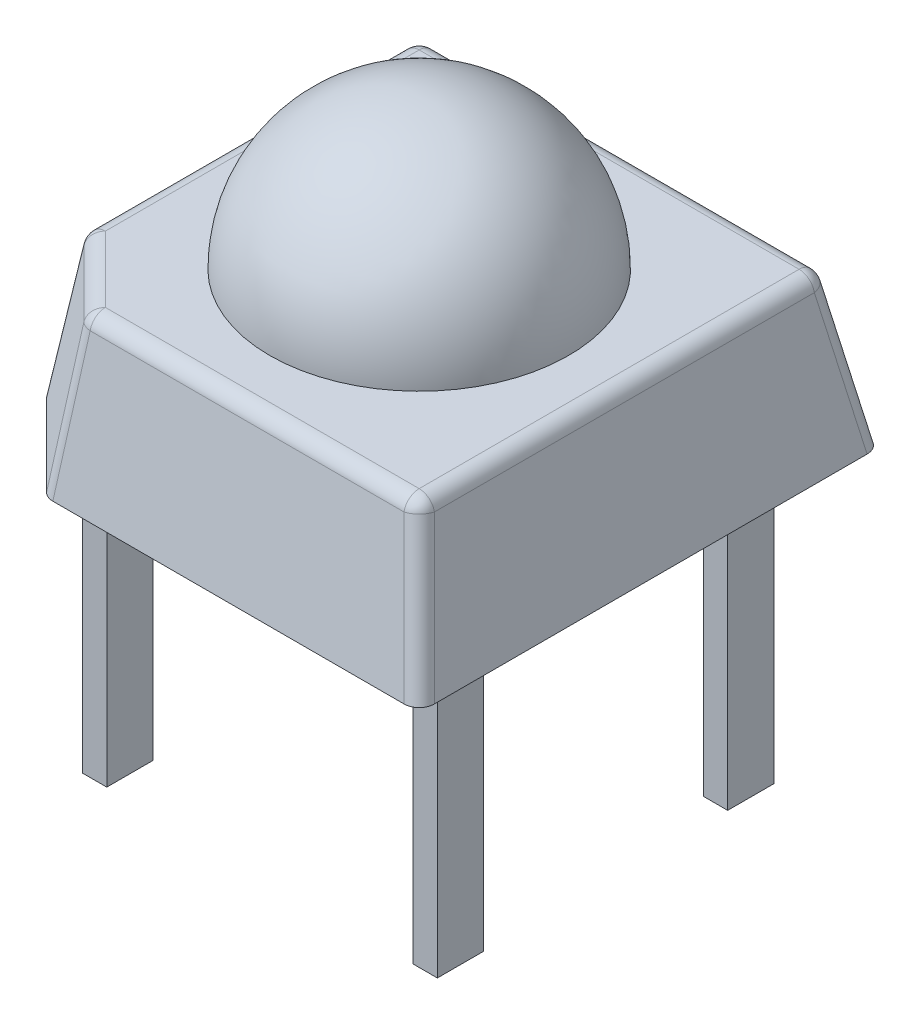
SolidWorks part; units mm, degrees
ref_plane "Front Plane" through (0, 0, 0) normal (0, 0, 1) x (1, 0, 0)
ref_plane "Top Plane" through (0, 0, 0) normal (0, 1, 0) x (1, 0, 0)
ref_plane "Right Plane" through (0, 0, 0) normal (1, 0, 0) x (0, 0, -1)
sketch "Sketch1" plane through (0, 0, 0) normal (0, 1, 0) x (1, 0, 0)
  line L0 (-3.825, -2.325) -> (-2.325, -3.825)
  line L1 (-3.825, 3.825) -> (3.825, 3.825)
  line L2 (-3.825, 3.825) -> (-3.825, -2.325)
  line L3 (-2.325, -3.825) -> (3.825, -3.825)
  line L4 (3.825, 3.825) -> (3.825, -3.825)
  point P4 (0, 3.825)
  point P6 (3.825, 0)
  dimension "D1" = 7.65
  dimension "D2" = 7.65
  dimension "D3" = 1.5
  dimension "D4" = 1.5
extrude "Boss-Extrude1" add sketch "Sketch1" along normal blind 2.5
chamfer "Chamfer1" distance 2.65 distance2 0.5 5 edges at (3.825, 2.5, 0) (0, 2.5, -3.825) (-3.825, 2.5, -0.75) (-3.075, 2.5, 3.075) (0.75, 2.5, 3.825) first distance on face at (3.825, 1.25, 0) first distance on face at (0, 1.25, -3.825) first distance on face at (-3.825, 1.25, -0.75) first distance on face at (-3.075, 1.25, 3.075) first distance on face at (0.75, 1.25, 3.825)
fillet "Fillet1" radius 0.254 10 edges at (-2.7214, 2.5, 2.7214) (-3.325, 2.5, -0.6036) (0, 2.5, -3.325) (3.325, 2.5, 0) (0.6036, 2.5, 3.325) (3.5608, 1.25, -3.5608) (3.5608, 1.25, 3.5608) (-3.5608, 1.25, -3.5608) (-3.5608, 1.25, 2.2156) (-2.2156, 1.25, 3.5608)
sketch "Sketch2" plane through (0, 2.5, 0) normal (0, 1, 0) x (1, 0, 0)
  line L0 (0, -2.45) -> (0, 2.45)
  arc A0 (0, -2.45) -> (0, 2.45) centre (0, 0) ccw
  dimension "D1" = 2.45
revolve "Revolve1" add sketch "Sketch2" angle 180 about L0 other way angle 180
sketch "Sketch3" plane through (0, 0, 0) normal (0, -1, 0) x (1, 0, 0)
  line L0 (-3.7967, 2.2099) -> (-3.7967, -3.5471) construction
  line L1 (-2.9077, 2.6144) -> (-2.5077, 2.6144)
  line L2 (-2.9077, 2.6144) -> (-2.9077, 1.8544)
  line L3 (-2.9077, 1.8544) -> (-2.5077, 1.8544)
  line L4 (-2.5077, 2.6144) -> (-2.5077, 1.8544)
  line L5 (-2.9077, -2.1456) -> (-2.5077, -2.1456)
  line L6 (-2.9077, -2.1456) -> (-2.9077, -2.9056)
  line L7 (-2.9077, -2.9056) -> (-2.5077, -2.9056)
  line L8 (-2.5077, -2.1456) -> (-2.5077, -2.9056)
  line L9 (2.5123, -2.1456) -> (2.9123, -2.1456)
  line L10 (2.5123, -2.1456) -> (2.5123, -2.9056)
  line L11 (2.5123, -2.9056) -> (2.9123, -2.9056)
  line L12 (2.9123, -2.1456) -> (2.9123, -2.9056)
  line L13 (2.5123, 2.6144) -> (2.9123, 2.6144)
  line L14 (2.5123, 2.6144) -> (2.5123, 1.8544)
  line L15 (2.5123, 1.8544) -> (2.9123, 1.8544)
  line L16 (2.9123, 2.6144) -> (2.9123, 1.8544)
  line L17 (-2.0307, 3.1144) -> (3.1144, 3.1144) construction
  dimension "D1" = 0.4
  dimension "D2" = 5.02
  dimension "D3" = 0.889
  dimension "D4" = 0.76
  dimension "D5" = 4
  dimension "D6" = 0.5
extrude "Boss-Extrude2" add sketch "Sketch3" along normal blind 4.8
